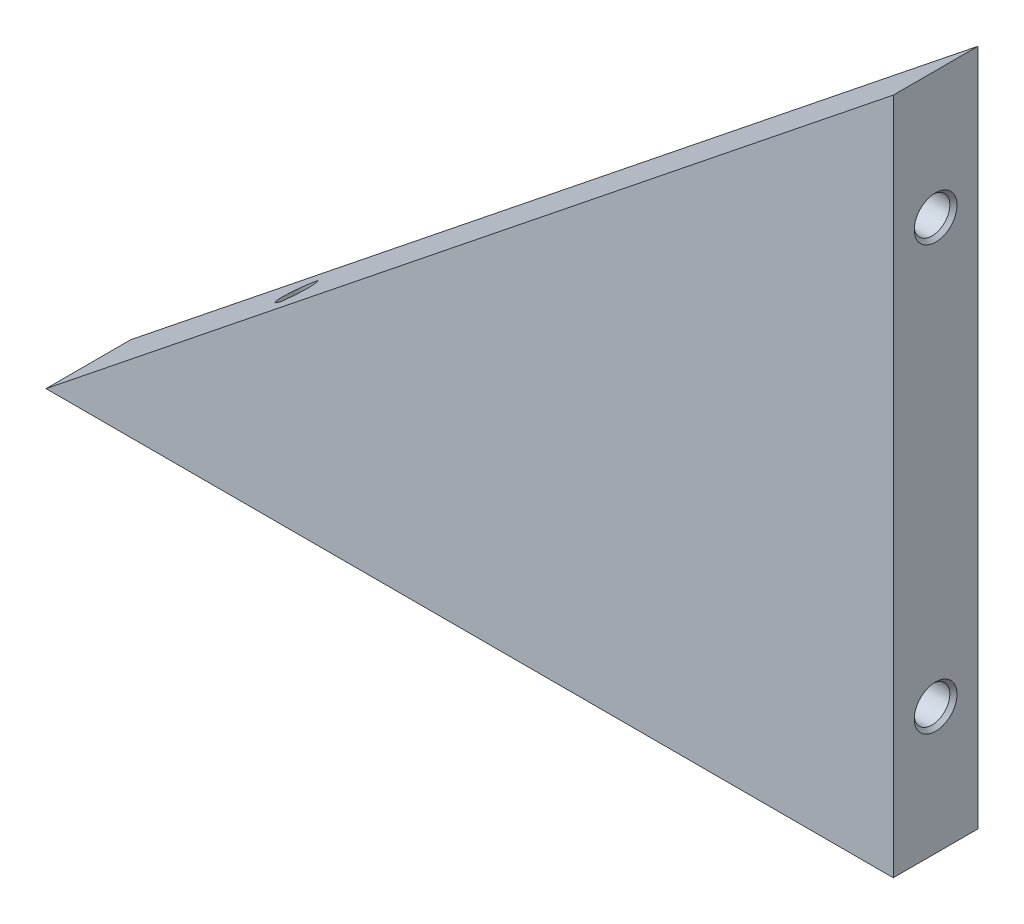
SolidWorks part; units mm, degrees
ref_plane "Vorne" through (0, 0, 0) normal (0, 0, 1) x (1, 0, 0)
ref_plane "Oben" through (0, 0, 0) normal (0, 1, 0) x (1, 0, 0)
ref_plane "Rechts" through (0, 0, 0) normal (1, 0, 0) x (0, 0, -1)
ref_plane "E_Boden" through (0, 1, 0) normal (0, 1, 0) x (1, 0, 0)
sketch "Skizze1" plane through (0, 0, 0) normal (0, 0, 1) x (1, 0, 0)
  line L0 (0, 10) -> (0, -9.5229) construction
  line L1 (-15.5467, 0) -> (14.4334, 0) construction
  line L2 (100, 0) -> (100, 80)
  line L3 (100, 80) -> (0, 0)
  line L4 (0, 0) -> (100, 0)
  dimension "D1" = 80
  dimension "D2" = 100
extrude "Aufsatz-Linear austragen1" add sketch "Skizze1" along normal blind 10
hole_wizard "M5 Gewindebohrung2" positions "Skizze7" profile "Skizze8" tap size "M5" standard "DIN"
sketch "Skizze7" plane through (100, 0, 0) normal (1, 0, 0) x (0, 0, -1)
  line L2 (-5, 80) -> (-5, 0) construction
  line L3 (-10, 80) -> (0, 80) construction
  line L4 (-10, 0) -> (0, 0) construction
  line L6 (-10, 40) -> (0, 40) construction
  line L7 (-10, 0) -> (-10, 80) construction
  line L8 (0, 0) -> (0, 80) construction
  point P0 (-5, 65)
  point P2 (-5, 15)
  dimension "D1" = 50
sketch "Skizze8" plane through (100, 65, 5) normal (0, 1, 0) x (0, 0, -1)
  line L0 (0, 0) -> (0, 16.2618)
  line L1 (0, 16.2618) -> (2.1, 15)
  line L2 (2.1, 15) -> (2.1, 0.425)
  line L3 (2.1, 0.425) -> (2.525, 0)
  line L5 (2.525, 0) -> (0, 0)
  line L6 (-2.1, 0.425) -> (-2.525, 0) construction
  line L10 (0, 16.2618) -> (-2.1, 15) construction
  line L11 (0, -6.35) -> (0, 107.95) construction
  dimension "Bohrerdurchmesser" = 4.2
  dimension "Bohrungstiefe" = 15
  dimension "Senkdurchmesser (Oben)" = 5.05
  dimension "Senkwinkel (Oben)" = 90
  dimension "Spitzenwinkel" = 118
cosmetic thread "Bohrungsgewinde3" parameters "D1"=10, "D2"=5
cosmetic thread "Bohrungsgewinde4" parameters "D1"=10, "D2"=5
hole_wizard "M5 Gewindebohrung3" positions "Skizze9" profile "Skizze10" tap size "M5" standard "DIN"
sketch "Skizze9" plane through (0, 0, 0) normal (0, -1, 0) x (-1, 0, 0)
  line L0 (-100, -5) -> (0, -5) construction
  line L1 (-100, -10) -> (-100, 0) construction
  line L2 (0, -10) -> (0, 0) construction
  line L4 (-50, 0) -> (-50, -10) construction
  line L5 (0, 0) -> (-100, 0) construction
  line L6 (0, -10) -> (-100, -10) construction
  point P0 (-25, -5)
  point P2 (-75, -5)
  dimension "D1" = 50
sketch "Skizze10" plane through (25, 0, 5) normal (1, 0, 0) x (0, 0, -1)
  line L0 (0, 0) -> (0, 21.2618)
  line L1 (0, 21.2618) -> (2.1, 20)
  line L2 (2.1, 20) -> (2.1, 0.425)
  line L3 (2.1, 0.425) -> (2.525, 0)
  line L5 (2.525, 0) -> (0, 0)
  line L6 (-2.1, 0.425) -> (-2.525, 0) construction
  line L10 (0, 21.2618) -> (-2.1, 20) construction
  line L11 (0, -6.35) -> (0, 107.95) construction
  dimension "Bohrerdurchmesser" = 4.2
  dimension "Bohrungstiefe" = 20
  dimension "Senkdurchmesser (Oben)" = 5.05
  dimension "Senkwinkel (Oben)" = 90
  dimension "Spitzenwinkel" = 118
cosmetic thread "Bohrungsgewinde5" parameters "D1"=10, "D2"=5
cosmetic thread "Bohrungsgewinde6" parameters "D1"=10, "D2"=5
